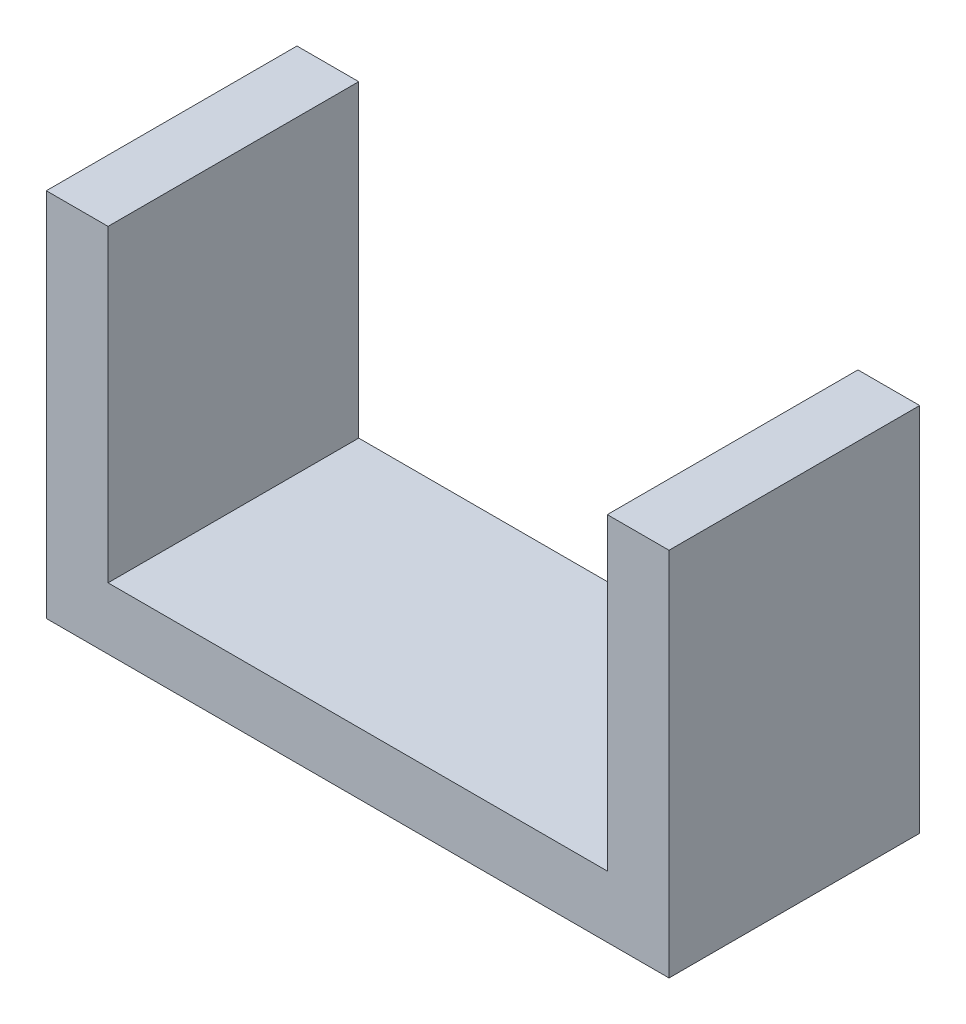
SolidWorks part; units mm, degrees
ref_plane "Front Plane" through (0, 0, 0) normal (0, 0, 1) x (1, 0, 0)
ref_plane "Top Plane" through (0, 0, 0) normal (0, 1, 0) x (1, 0, 0)
ref_plane "Right Plane" through (0, 0, 0) normal (1, 0, 0) x (0, 0, -1)
sketch "Sketch1" plane through (0, 0, 0) normal (0, 1, 0) x (1, 0, 0)
  line L1 (0, 0) -> (50.43, 0)
  line L2 (0, 0) -> (0, 20.3)
  line L3 (0, 20.3) -> (50.43, 20.3)
  line L4 (50.43, 0) -> (50.43, 20.3)
  dimension "D1" = 50.43
  dimension "D2" = 20.3
extrude "YawMount" add sketch "Sketch1" along normal blind 5
sketch "Sketch2" plane through (0, 5, 0) normal (0, 1, 0) x (1, 0, 0)
  line L0 (0, 0) -> (50.43, 0) construction
  line L1 (0, 20.3) -> (5, 20.3)
  line L2 (0, 20.3) -> (0, 0)
  line L3 (0, 0) -> (5, 0)
  line L4 (5, 20.3) -> (5, 0)
  line L6 (50.43, 20.3) -> (45.43, 20.3)
  line L7 (50.43, 20.3) -> (50.43, 0)
  line L8 (50.43, 0) -> (45.43, 0)
  line L9 (45.43, 20.3) -> (45.43, 0)
  dimension "D2" = 5
extrude "BodyConnectors" add sketch "Sketch2" along normal blind 25
equation "\"srv_w\"= 40.43mm'width of Sain Smart SR319"
equation "\"D1@Sketch1\"=\"srv_w\" + \"mnt_thick\"*2"
equation "\"srv_h\" = 40.61mm'height of Sain Smart SR319"
equation "\"srv_d\"= 20.3mm'depth of Sain Smart SR319"
equation "\"D2@Sketch1\"=\"srv_d\""
equation "\"mnt_thick\"= 5mm'thickness of bracket"
equation "\"D1@YawMount\" = \"mnt_thick\""
equation "\"D2@Sketch2\"=\"mnt_thick\""
equation "\"D1@Sketch2\"=\"mnt_thick\""
